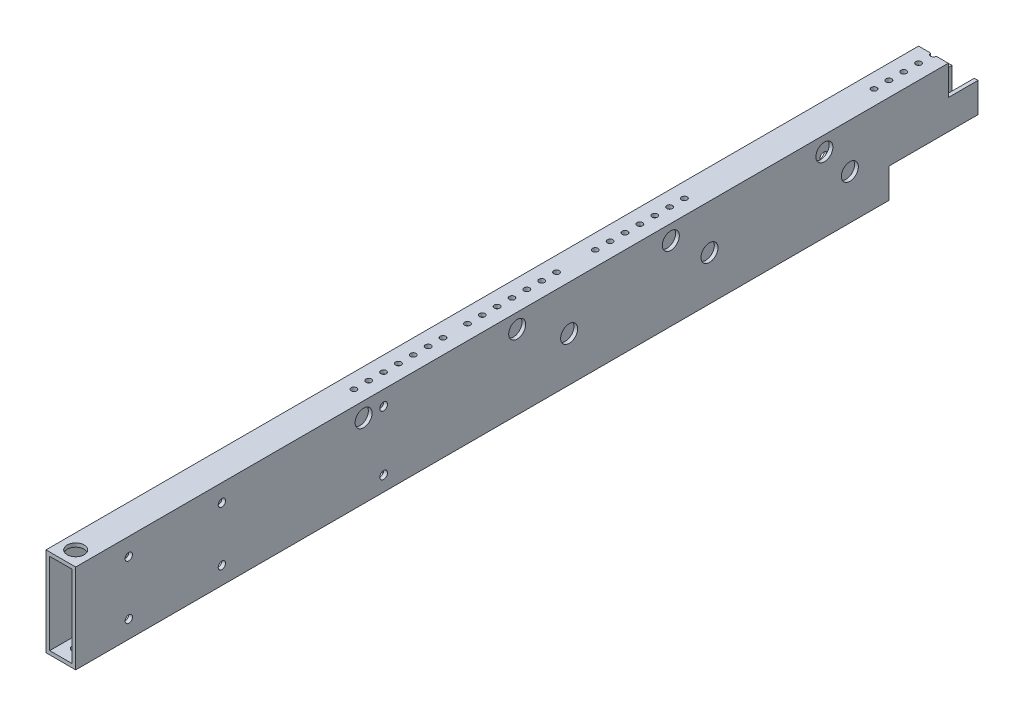
SolidWorks part; units mm, degrees
ref_plane "Front Plane" through (0, 0, 0) normal (0, 0, 1) x (1, 0, 0)
ref_plane "Top Plane" through (0, 0, 0) normal (0, 1, 0) x (1, 0, 0)
ref_plane "Right Plane" through (0, 0, 0) normal (1, 0, 0) x (0, 0, -1)
sketch "Sketch1" plane through (0, 0, 0) normal (0, 0, 1) x (1, 0, 0)
  line L1 (-12.7, -38.1) -> (12.7, -38.1)
  line L2 (-12.7, -38.1) -> (-12.7, 38.1)
  line L3 (-12.7, 38.1) -> (12.7, 38.1)
  line L4 (12.7, -38.1) -> (12.7, 38.1)
  line L5 (-12.7, -38.1) -> (12.7, 38.1) construction
  line L6 (-12.7, 38.1) -> (12.7, -38.1) construction
  point P0 (0, 0)
  dimension "D1" = 25.4
  dimension "D2" = 76.2
extrude "Boss-Extrude1" add sketch "Sketch1" along normal mid plane 771.398
shell "Shell1" thickness 3.175 removed face at (0, 0, -385.699) removed face at (0, 0, 385.699)
sketch "Sketch2" plane through (12.7, 0, 0) normal (1, 0, 0) x (0, 0, -1)
  line L1 (385.699, -38.1) -> (309.499, -38.1)
  line L2 (385.699, -38.1) -> (385.699, -12.7)
  line L3 (385.699, -12.7) -> (309.499, -12.7)
  line L4 (309.499, -38.1) -> (309.499, -12.7)
  dimension "D1" = 25.4
  dimension "D2" = 76.2
extrude "Cut-Extrude1" cut sketch "Sketch2" against normal through all
sketch "Sketch3" plane through (12.7, 0, 0) normal (1, 0, 0) x (0, 0, -1)
  line L1 (385.699, 38.1) -> (360.299, 38.1)
  line L2 (385.699, 38.1) -> (385.699, 12.7)
  line L3 (385.699, 12.7) -> (360.299, 12.7)
  line L4 (360.299, 38.1) -> (360.299, 12.7)
  dimension "D1" = 25.4
extrude "Cut-Extrude2" cut sketch "Sketch3" against normal through all
sketch "Sketch4" plane through (0, 38.1, 0) normal (0, 1, 0) x (1, 0, 0)
  line L0 (-12.7, 360.299) -> (12.7, 360.299) construction
  circle A0 centre (0, 147.3945) radius 2.3812
  circle A1 centre (0, 134.6945) radius 2.3812
  circle A2 centre (0, 121.9945) radius 2.3812
  circle A3 centre (0, 109.2945) radius 2.3812
  circle A4 centre (0, 96.5945) radius 2.3812
  circle A5 centre (0, 83.8945) radius 2.3812
  circle A6 centre (0, 71.1945) radius 2.3812
  circle A7 centre (0, 38.0987) radius 2.3812
  circle A8 centre (0, 25.3987) radius 2.3813
  circle A9 centre (0, 12.6987) radius 2.3813
  circle A10 centre (0, -0.0013) radius 2.3813
  circle A11 centre (0, -12.7013) radius 2.3812
  circle A12 centre (0, -25.4013) radius 2.3812
  circle A13 centre (0, -38.1013) radius 2.3812
  circle A15 centre (0, -58.9932) radius 2.3812
  circle A16 centre (0, -71.6932) radius 2.3812
  circle A17 centre (0, -84.3932) radius 2.3812
  circle A18 centre (0, -97.0932) radius 2.3812
  circle A19 centre (0, -109.7932) radius 2.3812
  circle A20 centre (0, -122.4932) radius 2.3812
  circle A21 centre (0, -135.1932) radius 2.3813
  point P33 (0, 360.299)
  dimension "D1" = 4.7625
  dimension "D3" = 12.7
  dimension "D4" = 12.7
  dimension "D5" = 12.7
  dimension "D6" = 12.7
  dimension "D7" = 12.7
  dimension "D8" = 12.7
  dimension "D9" = 322.2003
  dimension "D10" = 12.7
  dimension "D11" = 12.7
  dimension "D12" = 12.7
  dimension "D13" = 12.7
  dimension "D14" = 12.7
  dimension "D15" = 12.7
  dimension "D16" = 12.7
  dimension "D17" = 419.2922
  dimension "D18" = 12.7
  dimension "D19" = 12.7
  dimension "D20" = 12.7
  dimension "D21" = 12.7
  dimension "D22" = 12.7
  dimension "D2" = 212.9045
extrude "Cut-Extrude3" cut sketch "Sketch4" against normal through all
sketch "Sketch5" plane through (0, 38.1, 0) normal (0, 1, 0) x (1, 0, 0)
  line L0 (-12.7, 360.299) -> (12.7, 360.299) construction
  circle A0 centre (0, 360.299) radius 2.3813
  circle A1 centre (0, 347.599) radius 2.3813
  circle A2 centre (0, 334.899) radius 2.3813
  circle A3 centre (0, 322.199) radius 2.3813
  circle A4 centre (0, 309.499) radius 2.3813
  dimension "D1" = 4.7625
  dimension "D3" = 12.7
  dimension "D4" = 12.7
  dimension "D5" = 12.7
  dimension "D8" = 0
  dimension "D2" = 12.7
extrude "Cut-Extrude4" cut sketch "Sketch5" against normal up to next
sketch "Sketch6" plane through (0, -38.1, 0) normal (0, -1, 0) x (1, 0, 0)
  line L0 (-12.7, -309.499) -> (12.7, -309.499) construction
  circle A0 centre (0, -309.499) radius 2.3813
  circle A1 centre (0, -296.799) radius 2.3813
  circle A2 centre (0, -284.099) radius 2.3813
  circle A3 centre (0, -258.699) radius 2.3813
  circle A6 centre (0, -271.399) radius 2.3813
  dimension "D1" = 4.7625
  dimension "D2" = 12.7
  dimension "D3" = 12.7
  dimension "D4" = 12.7
  dimension "D5" = 12.7
  dimension "D6" = 0
extrude "Cut-Extrude5" cut sketch "Sketch6" against normal up to next
sketch3d "3DSketch1" [suppressed]
  line L0 (0, 34.925, -109.2945) -> (0, 38.1, -109.2945) construction
  line L1 (0, 34.925, 97.0932) -> (0, 38.1, 97.0932) construction
  point P0 (0, 38.1, -109.2945)
  point P1 (0, 0, 0)
  point P4 (0, 38.1, 97.0932)
sketch "Sketch11" plane through (12.7, 0, 0) normal (1, 0, 0) x (0, 0, -1)
  point P0 (-340.3244, 23.1254)
  point P1 (-260.7244, 23.1254)
  point P3 (-260.7244, -23.1)
  point P5 (-340.3244, -23.1)
hole_wizard "CBORE for M6 Hex Head Bolt1" positions "Sketch19" profile "Sketch18" counterbore size "M6" standard "Lanco STD" end condition through all
sketch "Sketch19" plane through (-12.7, 0, 0) normal (-1, 0, 0) x (0, 0, 1)
  point P0 (260.7244, 23.1254)
  point P3 (260.7244, -23.1)
  point P6 (340.3244, 23.1254)
  point P9 (340.3244, -23.1)
sketch "Sketch18" plane through (-12.7, 23.1254, 260.7244) normal (0, 1, 0) x (0, 0, 1)
  line L0 (0, 0) -> (0, 25.4)
  line L1 (0, 25.4) -> (3.15, 25.4)
  line L3 (3.15, 25.4) -> (3.15, 4)
  line L4 (3.15, 4) -> (7.2735, 4)
  line L5 (7.2735, 4) -> (7.2735, 0)
  line L7 (7.2735, 0) -> (0, 0)
  line L11 (0, -6.35) -> (0, 107.95) construction
  dimension "Thru Hole Dia." = 6.3
  dimension "Thru Hole Depth" = 25.4
  dimension "C'Bore Dia." = 14.547
  dimension "C'Bore Depth" = 4
hole_wizard "CBORE for M6 Hex Head Cap Screw1" positions "Sketch21" profile "Sketch20" counterbore size "M6" standard "ANSI Metric" end condition through all
sketch "Sketch21" plane through (-12.7, 0, 0) normal (-1, 0, 0) x (0, 0, 1)
  line L0 (385.699, 38.1) -> (-360.299, 38.1) construction
  line L1 (385.699, 38.1) -> (385.699, -38.1) construction
  point P0 (122.4678, 25.4)
  point P2 (122.4678, -25.4)
  dimension "D1" = 12.7
  dimension "D2" = 63.5
  dimension "D3" = 263.2312
  dimension "D4" = 263.2312
sketch "Sketch20" plane through (-12.7, 25.4, 122.4678) normal (0, 1, 0) x (0, 0, 1)
  line L0 (0, 0) -> (0, 25.4)
  line L1 (0, 25.4) -> (3.3, 25.4)
  line L3 (3.3, 25.4) -> (3.3, 4.15)
  line L4 (3.3, 4.15) -> (7.275, 4.15)
  line L5 (7.275, 4.15) -> (7.275, 0)
  line L7 (7.275, 0) -> (0, 0)
  line L11 (0, -6.35) -> (0, 107.95) construction
  dimension "Thru Hole Dia." = 6.6
  dimension "Thru Hole Depth" = 25.4
  dimension "C'Bore Dia." = 14.55
  dimension "C'Bore Depth" = 4.15
hole_wizard "CBORE for M6 Hex Head Cap Screw2" positions "Sketch26" profile "Sketch25" counterbore size "M6" standard "ANSI Metric" end condition through all
sketch "Sketch26" plane through (0, 38.1, 0) normal (0, 1, 0) x (1, 0, 0)
  line L0 (12.7, -385.699) -> (-12.7, -385.699) construction
  point P0 (0, -372.999)
  dimension "D1" = 12.7
sketch "Sketch25" plane through (0, 38.1, 372.999) normal (1, 0, 0) x (0, 0, 1)
  line L0 (0, 0) -> (0, 76.2)
  line L1 (0, 76.2) -> (3.3, 76.2)
  line L3 (3.3, 76.2) -> (3.3, 4.15)
  line L4 (3.3, 4.15) -> (7.275, 4.15)
  line L5 (7.275, 4.15) -> (7.275, 0)
  line L7 (7.275, 0) -> (0, 0)
  line L11 (0, -6.35) -> (0, 107.95) construction
  dimension "Thru Hole Dia." = 6.6
  dimension "Thru Hole Depth" = 76.2
  dimension "C'Bore Dia." = 14.55
  dimension "C'Bore Depth" = 4.15
hole_wizard "CBORE for M6 Hex Head Cap Screw3" positions "Sketch28" profile "Sketch27" counterbore size "M6" standard "ANSI Metric" end condition through all
sketch "Sketch28" plane through (12.7, 0, 0) normal (1, 0, 0) x (0, 0, -1)
  point P9 (36.1449, 0)
  point P13 (156.1449, 0)
  point P15 (276.1449, 0)
sketch "Sketch27" plane through (12.7, 0, -36.1449) normal (0, 1, 0) x (0, 0, -1)
  line L0 (0, 0) -> (0, 25.4)
  line L1 (0, 25.4) -> (3.3, 25.4)
  line L3 (3.3, 25.4) -> (3.3, 4.15)
  line L4 (3.3, 4.15) -> (7.275, 4.15)
  line L5 (7.275, 4.15) -> (7.275, 0)
  line L7 (7.275, 0) -> (0, 0)
  line L11 (0, -6.35) -> (0, 107.95) construction
  dimension "Thru Hole Dia." = 6.6
  dimension "Thru Hole Depth" = 25.4
  dimension "C'Bore Dia." = 14.55
  dimension "C'Bore Depth" = 4.15
hole_wizard "CBORE for M6 Hex Head Bolt2" positions "Sketch32" profile "Sketch31" counterbore size "M6" standard "DIN" end condition through all
sketch "Sketch32" plane through (12.7, 0, 0) normal (1, 0, 0) x (0, 0, -1)
  line L0 (-385.699, 38.1) -> (360.299, 38.1) construction
  line L2 (385.699, -12.7) -> (385.699, 12.7) construction
  point P0 (254.381, 25.4)
  point P2 (123.063, 25.4)
  point P4 (-8.255, 25.4)
  point P6 (-139.573, 25.4)
  point P15 (385.699, 0)
  dimension "D1" = 12.7
  dimension "D2" = 131.318
  dimension "D3" = 131.318
  dimension "D4" = 131.318
  dimension "D5" = 131.318
sketch "Sketch31" plane through (12.7, 25.4, -254.381) normal (0, 1, 0) x (0, 0, -1)
  line L0 (0, 0) -> (0, 25.4)
  line L1 (0, 25.4) -> (3.15, 25.4)
  line L3 (3.15, 25.4) -> (3.15, 4)
  line L4 (3.15, 4) -> (7.2735, 4)
  line L5 (7.2735, 4) -> (7.2735, 0)
  line L7 (7.2735, 0) -> (0, 0)
  line L11 (0, -6.35) -> (0, 107.95) construction
  dimension "Thru Hole Dia." = 6.3
  dimension "Thru Hole Depth" = 25.4
  dimension "C'Bore Dia." = 14.547
  dimension "C'Bore Depth" = 4
equation "\"5.1`7\"=2.30417"
